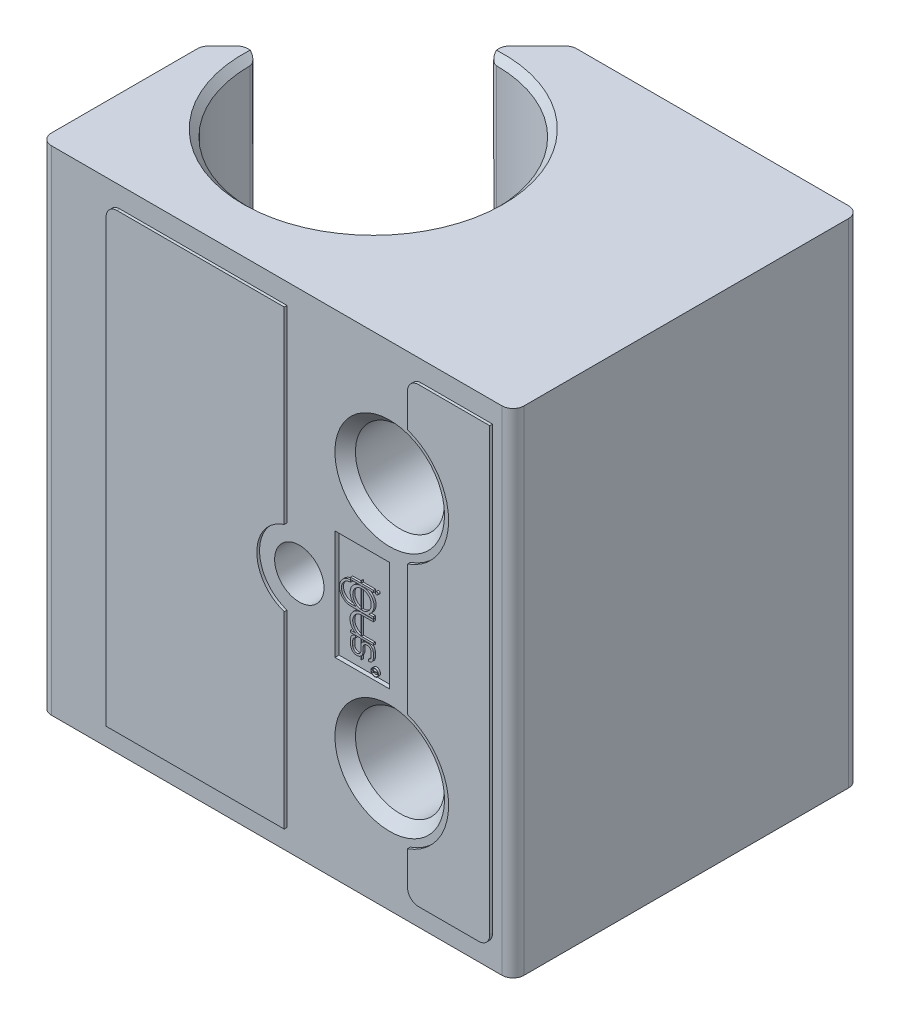
SolidWorks part; units mm, degrees
ref_plane "Front Plane" through (0, 0, 0) normal (0, 0, 1) x (1, 0, 0)
ref_plane "Top Plane" through (0, 0, 0) normal (0, 1, 0) x (1, 0, 0)
ref_plane "Right Plane" through (0, 0, 0) normal (1, 0, 0) x (0, 0, -1)
ref_plane "Plane1" through (0, 80.199, 0) normal (0, 1, 0) x (1, 0, 0)
sketch "Sketch1" plane through (0, 80.199, 0) normal (0, 1, 0) x (1, 0, 0)
  line L0 (28.5, 31) -> (28.5, 29.9861)
  line L1 (20.0139, 21.5) -> (19, 21.5)
  line L2 (19, 21.5) -> (17.5, 20)
  line L3 (17.5, 20) -> (17.5, 8.2)
  line L4 (17.5, 8.2) -> (52, 8.2)
  line L5 (52, 8.2) -> (52, 33.5)
  line L6 (52, 33.5) -> (31, 33.5)
  line L7 (31, 33.5) -> (28.5, 31)
  arc A0 (28.5, 29.9861) -> (20.0139, 21.5) centre (29, 21) cw
extrude "Boss-Extrude1" add sketch "Sketch1" against normal blind 16.2
sketch "Sketch2" plane through (0, 80.199, 0) normal (0, 1, 0) x (-1, 0, 0)
  line L0 (-28.5, -30.9875) -> (-28.5, -31)
  line L1 (-28.5, -31) -> (-31, -33.5)
  line L2 (-31, -33.5) -> (-52, -33.5)
  line L3 (-52, -33.5) -> (-52, -8.2)
  line L4 (-52, -8.2) -> (-17.5, -8.2)
  line L5 (-17.5, -8.2) -> (-17.5, -20)
  line L6 (-17.5, -20) -> (-19, -21.5)
  line L7 (-19, -21.5) -> (-19.0125, -21.5)
  arc A0 (-19.0125, -21.5) -> (-28.5, -30.9875) centre (-29, -21) ccw
extrude "Boss-Extrude2" add sketch "Sketch2" along normal blind 3.6
sketch "Sketch3" plane through (0, 83.799, 0) normal (0, 1, 0) x (-1, 0, 0)
  line L0 (-28.5, -21.5) -> (-28.5, -31)
  line L1 (-28.5, -31) -> (-31, -33.5)
  line L2 (-31, -33.5) -> (-52, -33.5)
  line L3 (-52, -33.5) -> (-52, -8.2)
  line L4 (-52, -8.2) -> (-17.5, -8.2)
  line L5 (-17.5, -8.2) -> (-17.5, -20)
  line L6 (-17.5, -20) -> (-19, -21.5)
  line L7 (-19, -21.5) -> (-28.5, -21.5)
extrude "Boss-Extrude3" add sketch "Sketch3" along normal blind 16.2
hole_wizard "Hole1" positions "Sketch5" profile "Sketch4" legacy
sketch "Sketch5" plane through (0, 83.799, 0) normal (0, -1, 0) x (-1, 0, 0)
  point P0 (-29, 21)
sketch "Sketch4" plane through (29, 83.799, -21) normal (1, 0, 0) x (0, 0, -1)
  line L0 (0, 0) -> (0, 16.2)
  line L1 (0, 16.2) -> (9, 16.2)
  line L2 (9, 16.2) -> (9, 0)
  line L3 (9, 0) -> (0, 0)
  line L4 (0, 110) -> (0, -10) construction
  dimension "Diameter" = 18
  dimension "Depth" = 16.2
sketch "Sketch6" plane through (0, 0, -8.2) normal (0, 0, 1) x (1, 0, 0)
  line L0 (44.5, 98.499) -> (50.5, 98.499)
  line L1 (50.5, 98.499) -> (50.5, 65.499)
  line L2 (50.5, 65.499) -> (44.5, 65.499)
  line L3 (44.5, 65.499) -> (44.5, 68.7564)
  line L4 (44.5, 77.2416) -> (44.5, 86.7564)
  line L5 (44.5, 95.2416) -> (44.5, 98.499)
  arc A0 (44.5, 68.7564) -> (44.5, 77.2416) centre (43, 72.999) ccw
  arc A1 (44.5, 86.7564) -> (44.5, 95.2416) centre (43, 90.999) ccw
extrude "Boss-Extrude4" add sketch "Sketch6" along normal blind 0.2
sketch "Sketch7" plane through (0, 0, -8.2) normal (0, 0, 1) x (1, 0, 0)
  line L0 (35.5, 65.499) -> (22.5, 65.499)
  line L1 (22.5, 65.499) -> (22.5, 98.499)
  line L2 (22.5, 98.499) -> (35.5, 98.499)
  line L3 (35.5, 98.499) -> (35.5, 84.7558)
  line L4 (35.5, 79.2422) -> (35.5, 65.499)
  arc A0 (35.5, 84.7558) -> (35.5, 79.2422) centre (36.4, 81.999) ccw
extrude "Boss-Extrude5" add sketch "Sketch7" along normal blind 0.2
sketch "Sketch8" plane through (0, 0, -8.2) normal (0, 0, 1) x (1, 0, 0)
  line L0 (39, 77.999) -> (43, 77.999)
  line L1 (43, 77.999) -> (43, 85.999)
  line L2 (43, 85.999) -> (39, 85.999)
  line L3 (39, 85.999) -> (39, 77.999)
extrude "Cut-Extrude1" cut sketch "Sketch8" against normal blind 0.3
sketch "Sketch9" plane through (0, 0, -8.5) normal (0, 0, 1) x (1, 0, 0)
  circle A0 centre (41.75, 78.349) radius 0.275
extrude "Boss-Extrude6" add sketch "Sketch9" along normal blind 0.15
hole_wizard "Hole2" positions "Sketch11" profile "Sketch10" legacy
sketch "Sketch11" plane through (0, 0, -8.35) normal (0, 0, 1) x (1, 0, 0)
  point P0 (41.75, 78.349)
sketch "Sketch10" plane through (41.75, 78.349, -8.35) normal (1, 0, 0) x (0, -1, 0)
  line L0 (0, 0) -> (0, 25.15)
  line L1 (0, 25.15) -> (0.25, 25.15)
  line L2 (0.25, 25.15) -> (0.25, 0)
  line L3 (0.25, 0) -> (0, 0)
  line L4 (0, 110) -> (0, -10) construction
  dimension "Diameter" = 0.5
  dimension "Depth" = 25.15
ref_plane "Plane2" through (0, 0, -8.5) normal (0, 0, -1) x (-1, 0, 0)
sketch "Sketch12" plane through (0, 0, -8.5) normal (0, 0, -1) x (-1, 0, 0)
  line L0 (-41.925, 78.424) -> (-41.925, 78.349)
  line L1 (-41.75, 78.349) -> (-41.75, 78.3615)
  line L2 (-41.75, 78.3615) -> (-41.575, 78.2615)
  line L3 (-41.575, 78.2615) -> (-41.5747, 78.3759)
  line L4 (-41.5747, 78.3759) -> (-41.75, 78.3759)
  line L5 (-41.75, 78.3759) -> (-41.75, 78.4115)
  line L6 (-41.75, 78.4115) -> (-41.575, 78.4115)
  line L7 (-41.575, 78.4115) -> (-41.575, 78.424)
  line L8 (-41.575, 78.424) -> (-41.925, 78.424)
  arc A0 (-41.925, 78.349) -> (-41.75, 78.349) centre (-41.8375, 78.349) ccw
extrude "Boss-Extrude7" add sketch "Sketch12" against normal blind 0.15
sketch "Sketch13" plane through (0, 0, -8.35) normal (0, 0, 1) x (1, 0, 0)
  line L0 (41.7625, 78.4115) -> (41.7625, 78.349)
  line L1 (41.9125, 78.349) -> (41.9125, 78.4115)
  line L2 (41.9125, 78.4115) -> (41.7625, 78.4115)
  arc A0 (41.7625, 78.349) -> (41.9125, 78.349) centre (41.8375, 78.349) ccw
extrude "Cut-Extrude2" cut sketch "Sketch13" against normal blind 0.15
sketch "Sketch14" plane through (0, 0, -8.5) normal (0, 0, 1) x (1, 0, 0)
  line L0 (41.65, 80.149) -> (41.65, 79.999)
  line L1 (41.65, 79.999) -> (40.775, 79.999)
  line L2 (40.775, 79.999) -> (40.775, 79.699)
  line L3 (41.65, 79.549) -> (41.65, 79.174)
  line L4 (41.3, 78.824) -> (41.3, 78.974)
  line L5 (41.5, 79.224) -> (41.5, 79.499)
  line L6 (40.9, 79.499) -> (40.9, 79.224)
  line L7 (40.775, 78.9128) -> (40.775, 78.649)
  line L8 (40.775, 78.649) -> (40.75, 78.649)
  line L9 (40.75, 78.649) -> (40.75, 78.8886)
  line L10 (40, 79.224) -> (40, 79.624)
  line L11 (40.35, 79.974) -> (40.35, 79.824)
  line L12 (40.15, 79.574) -> (40.15, 79.224)
  line L13 (40.75, 79.224) -> (40.75, 79.999)
  line L14 (40.75, 79.999) -> (40, 79.999)
  line L15 (40, 79.999) -> (40, 80.149)
  line L16 (40, 80.149) -> (40.35, 80.149)
  line L17 (40.75, 81.649) -> (40.75, 81.674)
  line L18 (40.75, 81.674) -> (40, 81.674)
  line L19 (40, 83.324) -> (40, 83.174)
  line L20 (40, 81.824) -> (40.4, 81.824)
  line L21 (40.75, 83.324) -> (40.75, 83.349)
  line L22 (40.75, 83.349) -> (40, 83.349)
  line L23 (40, 83.349) -> (40, 83.499)
  line L24 (40, 83.499) -> (40.75, 83.499)
  line L25 (40.75, 83.499) -> (40.75, 83.649)
  line L26 (40.75, 83.649) -> (40.775, 83.649)
  line L27 (40.775, 83.649) -> (40.775, 83.499)
  line L28 (40.775, 83.499) -> (41.675, 83.499)
  line L29 (41.675, 83.499) -> (41.675, 83.349)
  line L30 (41.675, 83.349) -> (40.8, 83.349)
  line L31 (40.8, 83.349) -> (40.8, 83.324)
  line L32 (41.3, 81.824) -> (41.65, 81.824)
  line L33 (41.65, 81.824) -> (41.65, 81.674)
  line L34 (41.65, 81.674) -> (40.775, 81.674)
  line L35 (40.775, 81.674) -> (40.775, 81.649)
  line L36 (40.775, 81.649) -> (41.65, 81.649)
  line L37 (41.65, 81.649) -> (41.65, 81.499)
  line L38 (41.65, 81.499) -> (40.775, 81.499)
  line L39 (40.775, 81.499) -> (40.775, 80.1508)
  line L40 (40.825, 80.149) -> (41.65, 80.149)
  arc A0 (40.775, 79.699) -> (41.2, 79.949) centre (41.2, 79.4627) cw
  arc A1 (41.2, 79.949) -> (41.65, 79.549) centre (41.2472, 79.549) cw
  arc A2 (41.65, 79.174) -> (41.3, 78.824) centre (41.3, 79.174) cw
  arc A3 (41.3, 78.974) -> (41.5, 79.224) centre (41.2438, 79.224) ccw
  arc A4 (41.5, 79.499) -> (40.9, 79.499) centre (41.2, 79.499) ccw
  arc A5 (40.9, 79.224) -> (40.775, 78.9128) centre (40.45, 79.224) cw
  arc A6 (40.75, 78.8886) -> (40, 79.224) centre (40.45, 79.224) cw
  arc A7 (40, 79.624) -> (40.35, 79.974) centre (40.35, 79.624) cw
  arc A8 (40.35, 79.824) -> (40.15, 79.574) centre (40.4062, 79.574) ccw
  arc A9 (40.15, 79.224) -> (40.75, 79.224) centre (40.45, 79.224) ccw
  arc A10 (40.35, 80.149) -> (40.75, 81.649) centre (40.75, 80.8457) cw
  arc A11 (40, 81.674) -> (40, 83.324) centre (40, 82.499) cw
  arc A12 (40, 83.174) -> (40, 81.824) centre (40, 82.499) ccw
  arc A13 (40.4, 81.824) -> (40.75, 83.324) centre (40.75, 82.5332) cw
  arc A14 (40.8, 83.324) -> (41.3, 81.824) centre (40.8965, 82.5228) cw
  arc A15 (40.775, 80.1508) -> (40.825, 80.149) centre (40.825, 80.8261) ccw
extrude "Boss-Extrude8" add sketch "Sketch14" along normal blind 0.15
sketch "Sketch15" plane through (0, 0, -8.35) normal (0, 0, 1) x (1, 0, 0)
  line L0 (40.75, 80.1532) -> (40.75, 81.499)
  arc A0 (40.75, 81.499) -> (40.75, 80.1532) centre (40.825, 80.8261) ccw
extrude "Cut-Extrude3" cut sketch "Sketch15" against normal blind 0.15
sketch "Sketch16" plane through (0, 0, -8.35) normal (0, 0, 1) x (1, 0, 0)
  line L0 (40.75, 81.8282) -> (40.75, 83.1698)
  arc A0 (40.75, 83.1698) -> (40.75, 81.8282) centre (40.825, 82.499) ccw
extrude "Cut-Extrude4" cut sketch "Sketch16" against normal blind 0.15
sketch "Sketch17" plane through (0, 0, -8.35) normal (0, 0, 1) x (1, 0, 0)
  line L0 (40.775, 83.1721) -> (40.775, 81.8259)
  arc A0 (40.775, 81.8259) -> (40.775, 83.1721) centre (40.825, 82.499) ccw
extrude "Cut-Extrude5" cut sketch "Sketch17" against normal blind 0.15
draft "Draft1" type of draft neutral plane draft angle 29.745 faces to draft 1 face at (41.6624, 78.3759, -8.425) neutral plane through (41.75, 78.3759, -8.35) neutral plane normal (-1, 0, 0) parameters "D1"=29.745
ref_plane "Plane3" through (0, 83.424, 0) normal (0, -1, 0) x (1, 0, 0)
sketch "Sketch18" plane through (0, 83.424, 0) normal (0, -1, 0) x (1, 0, 0)
  line L0 (42, -8.35) -> (41.9, -8.35)
  line L1 (41.9, -8.35) -> (41.9, -8.5)
  line L2 (41.9, -8.5) -> (42, -8.5)
  line L3 (42, -8.5) -> (42, -8.35)
  line L4 (41.9, -8.35) -> (41.9, -8.5) construction
revolve "Revolve1" add sketch "Sketch18" angle 360 about L4 reverse direction yes
hole_wizard "Hole3" positions "Sketch20" profile "Sketch19" legacy
sketch "Sketch20" plane through (0, 0, -33.5) normal (0, 0, -1) x (-1, 0, 0)
  point P0 (-43, 72.999)
  point P1 (-43, 90.999)
sketch "Sketch19" plane through (43, 72.999, -33.5) normal (1, 0, 0) x (0, 1, 0)
  line L0 (0, 0) -> (0, 25.301)
  line L1 (0, 25.301) -> (3.25, 25.301)
  line L2 (3.25, 25.301) -> (3.25, 4)
  line L3 (3.25, 4) -> (6.5, 4)
  line L4 (6.5, 4) -> (6.5, 0)
  line L5 (6.5, 0) -> (0, 0)
  line L6 (0, 110) -> (0, -10) construction
  dimension "Diameter" = 6.5
  dimension "Depth" = 25.301
  dimension "C-Bore Diameter" = 13
  dimension "C-Bore Depth" = 4
hole_wizard "#5 Clearance Hole1" positions "Sketch22" profile "Sketch21" hole size "#5" standard "ANSI Inch"
sketch "Sketch22" plane through (0, 0, -8.2) normal (0, 0, 1) x (1, 0, 0)
  point P0 (36.4, 81.999)
sketch "Sketch21" plane through (36.4, 81.999, -8.2) normal (1, 0, 0) x (0, -1, 0)
  line L0 (0, 0) -> (0, 12.8)
  line L1 (0, 12.8) -> (1.8, 12.8)
  line L2 (1.8, 12.8) -> (1.8, 0)
  line L5 (1.8, 0) -> (0, 0)
  line L11 (0, -6.35) -> (0, 107.95) construction
  dimension "Thru Hole Dia." = 3.6
  dimension "Thru Hole Depth" = 12.8
chamfer "Chamfer1" distance 0.75 angle 45 4 edges at (46.25, 72.999, -8.2) (46.25, 90.999, -8.2) (39.75, 72.999, -29.5) (39.75, 90.999, -29.5)
chamfer "Chamfer2" distance 0.5 angle 45 2 edges at (35.364, 63.999, -14.636) (35.364, 99.999, -14.636)
fillet "Fillet1" radius 0.5 4 edges at (28.5, 91.649, -29.9861) (20.0139, 91.649, -21.5) (28.5, 72.349, -29.9861) (20.0139, 72.349, -21.5) tangent propagation no
fillet "Fillet2" radius 0.8 11 edges at (22.5, 98.499, -8.1) (50.5, 65.499, -8.1) (44.5, 98.499, -8.1) (19, 81.999, -21.5) (17.5, 81.999, -8.2) (17.5, 81.999, -20) (28.5, 81.999, -31) (52, 81.999, -8.2) (44.5, 65.499, -8.1) (52, 81.999, -33.5) (31, 81.999, -33.5) tangent propagation no
